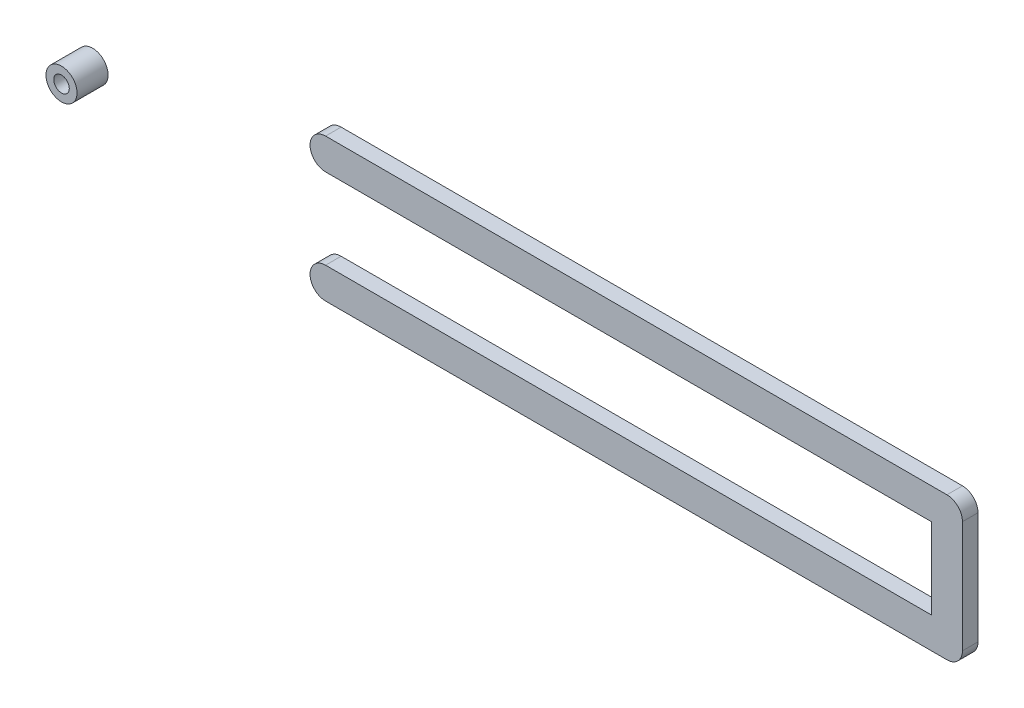
SolidWorks part; units mm, degrees
ref_plane "前视基准面" through (0, 0, 0) normal (0, 0, 1) x (1, 0, 0)
ref_plane "上视基准面" through (0, 0, 0) normal (0, 1, 0) x (1, 0, 0)
ref_plane "右视基准面" through (0, 0, 0) normal (1, 0, 0) x (0, 0, -1)
sketch "草图1" plane through (0, 0, 0) normal (0, 0, 1) x (1, 0, 0)
  line L0 (0, 0) -> (400, 0)
  line L1 (400, 0) -> (400, 52)
  line L2 (400, 52) -> (0, 52)
  line L3 (0, 52) -> (0, 72)
  line L4 (0, 72) -> (420, 72)
  line L5 (420, 72) -> (420, -20)
  line L6 (420, -20) -> (0, -20)
  line L7 (0, -20) -> (0, 0)
  circle A0 centre (-150, 26) radius 5
  circle A1 centre (-150, 26) radius 10
  point P12 (0, 0)
  point P13 (420, 26)
  dimension "D5" = 20
  dimension "D6" = 10
  dimension "D1" = 52
  dimension "D2" = 400
  dimension "D3" = 20
  dimension "D4" = 20
  dimension "D7" = 150
extrude "凸台-拉伸1" add sketch "草图1" along normal blind 10 contours L7 L6 L5 L4 L3 L2 L1 L0 region at (200, -4.2996, 0)
extrude "凸台-拉伸2" add sketch "草图1<3>" along normal blind 20 separate body contours A1 A0 region at (-159.7172, 26, 0)
sketch "草图1<3>" plane through (0, 0, 0) normal (0, 0, 1) x (1, 0, 0) same geometry as "草图1"
fillet "圆角1" radius 10 6 edges at (420, -20, 5) (420, 72, 5) (0, -20, 5) (0, 0, 5) (0, 52, 5) (0, 72, 5)
sketch "草图2" plane through (0, 0, 0) normal (0, 0, 1) x (1, 0, 0)
  point P0 (-150, 26)
